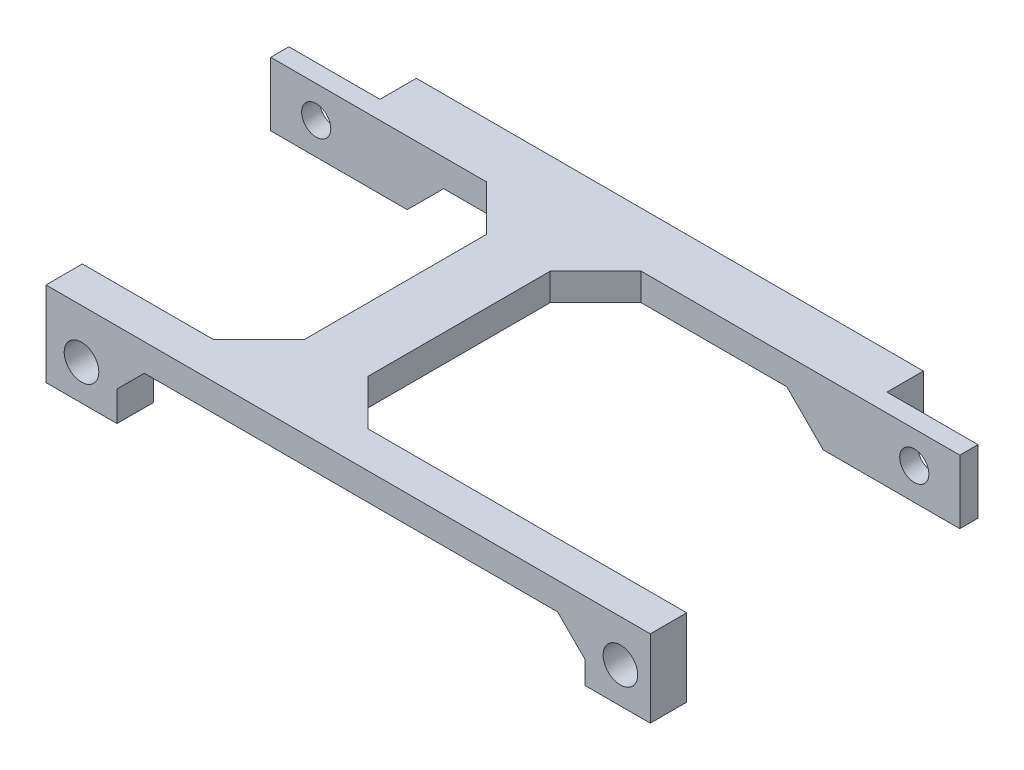
SolidWorks part; units mm, degrees
ref_plane "Płaszczyzna przednia" through (0, 0, 0) normal (0, 0, 1) x (1, 0, 0)
ref_plane "Płaszczyzna górna" through (0, 0, 0) normal (0, 1, 0) x (1, 0, 0)
ref_plane "Płaszczyzna prawa" through (0, 0, 0) normal (1, 0, 0) x (0, 0, -1)
sketch "Sketch2" plane through (0, -3.05, 0) normal (0, 1, 0) x (1, 0, 0)
  line L1 (79.3, 0) -> (69.3, 0)
  line L2 (79.3, 0) -> (79.3, -2)
  line L3 (79.3, -2) -> (69.3, -2)
  line L4 (69.3, 0) -> (69.3, -2)
  line L5 (3.6, 0) -> (13.6, 0)
  line L6 (3.6, 0) -> (3.6, -2)
  line L7 (3.6, -2) -> (13.6, -2)
  line L8 (13.6, 0) -> (13.6, -2)
  line L17 (69.3, -2) -> (13.6, -2)
  line L18 (69.3, -2) -> (69.3, 4)
  line L19 (69.3, 4) -> (13.6, 4)
  line L20 (13.6, -2) -> (13.6, 4)
  line L21 (32.3, -2) -> (39.3, -2)
  line L22 (32.3, -2) -> (32.3, -36)
  line L23 (32.3, -36) -> (39.3, -36)
  line L24 (39.3, -2) -> (39.3, -36)
  line M7 (71.3, 0) -> (79.3, 0)
  dimension "D1" = 2
  dimension "D2" = 10
  dimension "D3" = 10
  dimension "D4" = 2
  dimension "D5" = 30
  dimension "D6" = 55.7
  dimension "D7" = 7
  dimension "D8" = 34
  dimension "D9" = 4
extrude "Boss-Extrude1" add sketch "Sketch2" against normal blind 7 contours L3 L2 L1 M7 | L8 | L8 L5 L6 L7 | L22 L21 L24 L23 region at (74.3, -3.05, 1) region at (41.45, -3.05, -1) region at (8.6, -3.05, 1)
sketch "Sketch4" plane through (0, 0, -4) normal (0, 0, -1) x (-1, 0, 0)
  line L0 (-69.3, -10.05) -> (-13.6, -10.05) construction
  line L1 (-62.3, -10.05) -> (-20.6, -10.05)
  line L2 (-62.3, -10.05) -> (-62.3, -6.05)
  line L3 (-62.3, -6.05) -> (-20.6, -6.05)
  line L4 (-20.6, -10.05) -> (-20.6, -6.05)
  line L5 (-69.3, -3.05) -> (-13.6, -3.05) construction
  line L6 (-69.3, -10.05) -> (-69.3, -3.05) construction
  line L7 (-13.6, -10.05) -> (-13.6, -3.05) construction
  dimension "D1" = 3
  dimension "D2" = 7
  dimension "D3" = 7
extrude "Cut-Extrude1" cut sketch "Sketch4" against normal up to surface (40 mm away) up to face at (35.8, -6.55, 36)
sketch "Sketch6" plane through (0, 0, 36) normal (0, 0, 1) x (1, 0, 0)
  line L1 (79.3, -11.5551) -> (72.1165, -11.5551)
  line L2 (79.3, -11.5551) -> (79.3, -3.05)
  line L3 (79.3, -3.05) -> (72.1165, -3.05)
  line L4 (72.1165, -11.5551) -> (72.1165, -3.05)
  line L5 (20.7165, -12.3421) -> (12.9165, -12.3421)
  line L6 (20.7165, -12.3421) -> (20.7165, -3.05)
  line L7 (20.7165, -3.05) -> (12.9165, -3.05)
  line L8 (12.9165, -12.3421) -> (12.9165, -3.05)
  line L9 (32.3, -6.05) -> (39.3, -6.05) construction
  line L10 (72.1165, -3.05) -> (20.7165, -3.05)
  line L11 (72.1165, -3.05) -> (72.1165, -6.05)
  line L12 (72.1165, -6.05) -> (20.7165, -6.05)
  line L13 (20.7165, -3.05) -> (20.7165, -6.05)
  line L14 (32.3, -3.05) -> (39.3, -3.05) construction
  line L15 (79.3, -10.05) -> (79.3, -3.05) construction
  circle A0 centre (76.0165, -7.6551) radius 1.9
  circle A1 centre (16.8165, -8.4421) radius 1.9
  line M15 (39.3, -6.05) -> (39.3, -3.05)
  line M17 (32.3, -3.05) -> (32.3, -6.05)
  dimension "D3" = 3.8
  dimension "D4" = 3.8
  dimension "D7" = 3.9
  dimension "D10" = 3.9
  dimension "D12" = 3.9
  dimension "D1" = 0
  dimension "D2" = 0
  dimension "D5" = 0
  dimension "D6" = 3.9
  dimension "D8" = 0
  dimension "D9" = 0
  dimension "D11" = 3.9
  dimension "D13" = 0
  dimension "D14" = 0
extrude "Boss-Extrude2" add sketch "Sketch6" against normal blind 4 contours L12 L10 L6 M17 | L12 L4 L10 M15 | L4 L1 L2 L3 A0 | L8 L5 L6 L7 A1 region at (75.7082, -11.4438, 36) region at (55.7082, -4.55, 36) region at (26.5082, -4.55, 36) region at (20.5951, -9.196, 36)
chamfer "Chamfer1" distance 5 angle 45 4 edges at (39.3, -4.55, 32) (32.3, -4.55, 32) (32.3, -4.55, 2) (39.3, -4.55, 2)
chamfer "Chamfer2" distance 3 angle 45 2 edges at (72.1165, -6.05, 34) (20.7165, -6.05, 34)
chamfer "Chamfer7" distance 2 angle 45 4 edges at (62.3, -10.05, -1) (62.3, -6.05, -1) (20.6, -6.05, -1) (20.6, -10.05, -1)
sketch "Sketch7" plane through (0, 0, 0) normal (0, 0, -1) x (-1, 0, 0)
  circle A0 centre (-74.3, -6.55) radius 1.6
  circle A1 centre (-8.6, -6.55) radius 1.6
  dimension "D1" = 3.2
  dimension "D2" = 3.2
extrude "Cut-Extrude2" cut sketch "Sketch7" against normal blind 3.5
